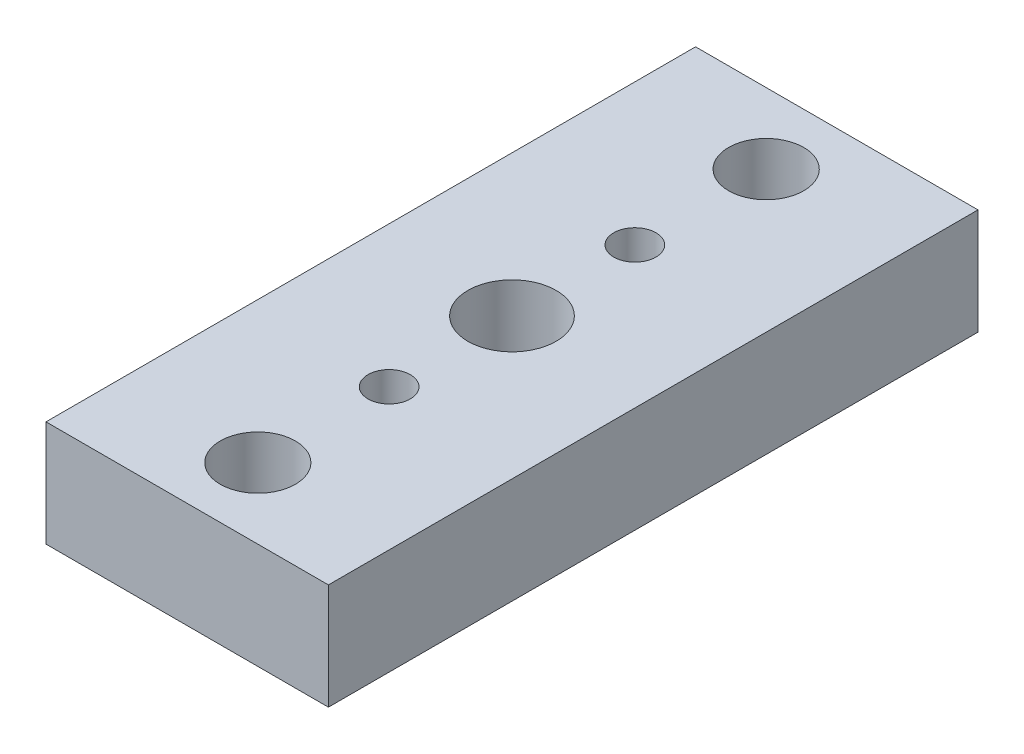
SolidWorks part; units mm, degrees
material "6061-T6 (SS)"
ref_plane "Front Plane" through (0, 0, 0) normal (0, 0, 1) x (1, 0, 0)
ref_plane "Top Plane" through (0, 0, 0) normal (0, 1, 0) x (1, 0, 0)
ref_plane "Right Plane" through (0, 0, 0) normal (1, 0, 0) x (0, 0, -1)
sketch "Sketch1" plane through (0, 0, 0) normal (0, 0, 1) x (1, 0, 0)
  line L0 (-12.7, -4.7625) -> (12.7, -4.7625)
  line L1 (-12.7, -4.7625) -> (-12.7, 4.7625)
  line L2 (12.7, -4.7625) -> (12.7, 4.7625)
  line L3 (-12.7, 4.7625) -> (12.7, 4.7625)
  line L4 (-12.7, -4.7625) -> (12.7, 4.7625) construction
  line L5 (12.7, -4.7625) -> (-12.7, 4.7625) construction
  point P1 (0, 0)
extrude "Extrude1" add sketch "Sketch1" along normal blind 58.42
sketch "Sketch2" plane through (0, 4.7625, 0) normal (0, 1, 0) x (1, 0, 0)
  line L0 (0, 0) -> (0, -6.35) construction
  line L1 (0, -58.42) -> (0, -52.07) construction
  line L2 (12.7, -58.42) -> (-12.7, -58.42) construction
  line L3 (-12.7, -29.21) -> (12.7, -29.21) construction
  line L4 (-12.7, -58.42) -> (-12.7, 0) construction
  line L5 (12.7, -58.42) -> (12.7, 0) construction
  line L6 (0, -29.21) -> (0, -40.259) construction
  point P13 (0, -29.21)
  dimension "D1" = 45.72
  dimension "D2" = 11.049
  dimension "D3" = 6.35
hole_wizard "1/4 Clearance Hole1" positions "3DSketch1" profile "Sketch3" hole size "1/4" standard "Ansi Inch"
sketch3d "3DSketch1"
  point P0 (0, 4.7625, 6.35)
  point P4 (0, 4.7625, 52.07)
sketch "Sketch3" plane through (0, 4.7625, 6.35) normal (1, 0, 0) x (0, 0, 1)
  line L0 (0, 0) -> (0, 14.7298)
  line L1 (0, 14.7298) -> (3.3782, 12.7)
  line L2 (3.3782, 12.7) -> (3.3782, 0)
  line L5 (3.3782, 0) -> (0, 0)
  line L10 (0, 14.7298) -> (-3.3782, 12.7) construction
  line L11 (0, -6.35) -> (0, 107.95) construction
  dimension "Hole Dia." = 6.7564
  dimension "Hole Depth" = 12.7
  dimension "Drill Angle" = 118
hole_wizard "3/8-16 Tapped Hole1" positions "3DSketch3" profile "Sketch5" tap size "3/8-16" standard "Ansi Inch" end condition through all
sketch3d "3DSketch3"
  point P0 (0, 4.7625, 29.21)
sketch "Sketch5" plane through (0, 4.7625, 29.21) normal (1, 0, 0) x (0, 0, 1)
  line L0 (0, 0) -> (0, 9.525)
  line L1 (0, 9.525) -> (3.9687, 9.525)
  line L2 (3.9687, 9.525) -> (3.9687, 0)
  line L5 (3.9687, 0) -> (0, 0)
  line L11 (0, -6.35) -> (0, 107.95) construction
  dimension "Thread Major Dia." = 7.9375
  dimension "Thru Tap Drill Depth" = 9.525
hole_wizard "#10-24 Tapped Hole1" positions "3DSketch4" profile "Sketch6" tap size "#10-24" standard "Ansi Inch" end condition through all
sketch3d "3DSketch4"
  point P0 (0, 4.7625, 40.259)
sketch "Sketch6" plane through (0, 4.7625, 40.259) normal (1, 0, 0) x (0, 0, 1)
  line L0 (0, 0) -> (0, 9.525)
  line L1 (0, 9.525) -> (1.8986, 9.525)
  line L2 (1.8986, 9.525) -> (1.8986, 0)
  line L5 (1.8986, 0) -> (0, 0)
  line L11 (0, -6.35) -> (0, 107.95) construction
  dimension "Thread Major Dia." = 3.7973
  dimension "Thru Tap Drill Depth" = 9.525
pattern_circular "CirPattern1" count 2 over 360 about axis through (0, 4.7625, 29.21) along (0, 1, 0) of "#10-24 Tapped Hole1"
